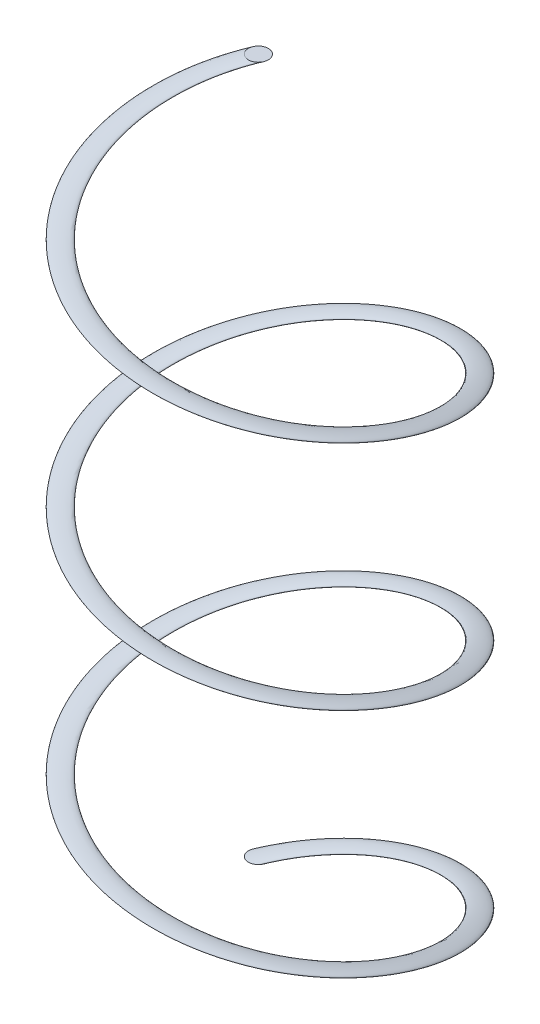
SolidWorks part; units mm, degrees
note: '?' marks a value the reader was unsure of.
ref_plane "Front Plane" through (0, 0, 0) normal (0, 0, 1) x (1, 0, 0)
ref_plane "Top Plane" through (0, 0, 0) normal (0, 1, 0) x (1, 0, 0)
ref_plane "Right Plane" through (0, 0, 0) normal (1, 0, 0) x (0, 0, -1)
sketch "Sketch2" plane through (0, 0, 0) normal (0, 1, 0) x (1, 0, 0)
  circle A0 centre (0, 0) radius 19.05
  dimension "D1" = 38.1
curve "Helix/Spiral1" pitch 29.5275 height 88.5825 turns 3
sketch "Sketch4" plane through (0, 0, 0) normal (0, 1, 0) x (1, 0, 0)
  circle A0 centre (-14.0847, 12.6057) radius 1.27
  dimension "D1" = 2.54
sweep "Sweep1" add profiles "Sketch4" path "Helix/Spiral1"
ref_axis "CentralAxis" through (0, -3.6015, 0) along (0, 1, 0)?
